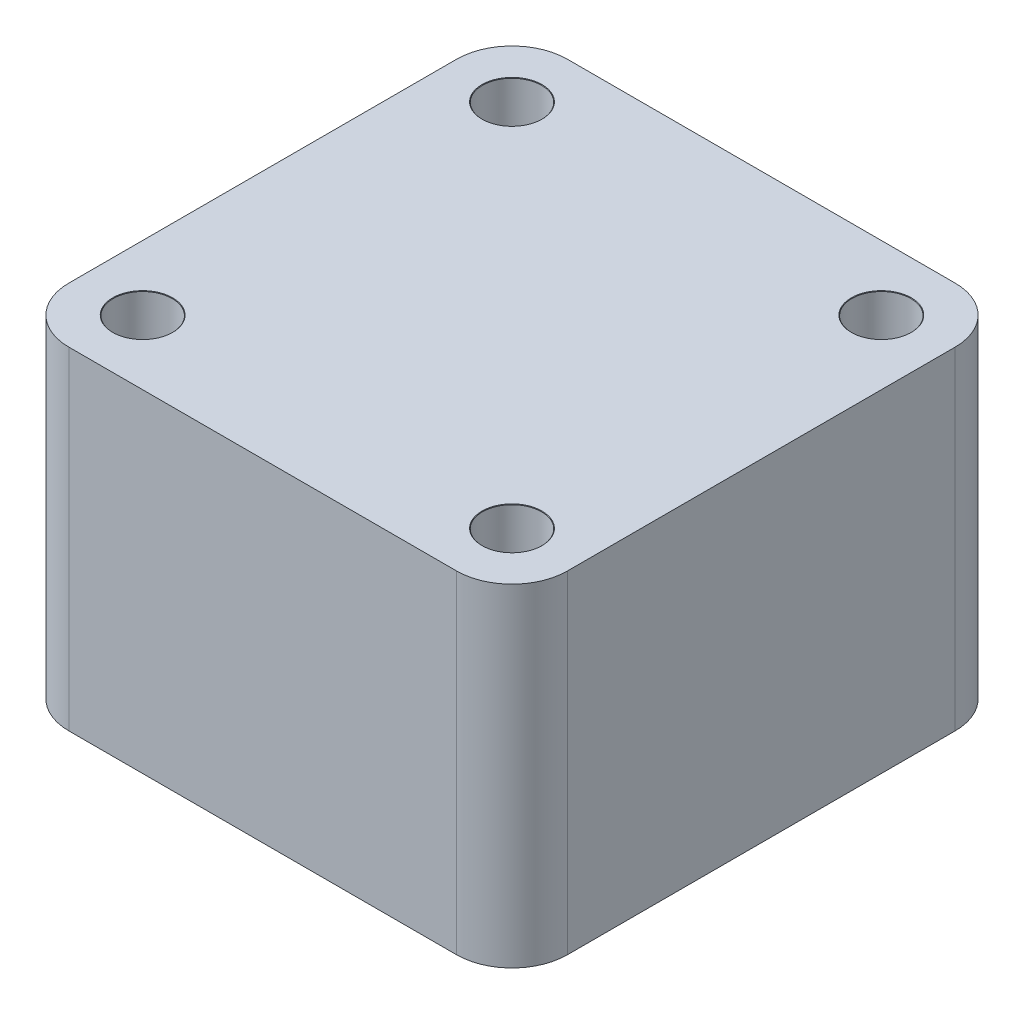
SolidWorks part; units mm, degrees
material "AISI 1045 Steel, cold drawn"
ref_plane "Front Plane" through (0, 0, 0) normal (0, 0, 1) x (1, 0, 0)
ref_plane "Top Plane" through (0, 0, 0) normal (0, 1, 0) x (1, 0, 0)
ref_plane "Right Plane" through (0, 0, 0) normal (1, 0, 0) x (0, 0, -1)
sketch "Sketch1" plane through (0, 0, 0) normal (0, 1, 0) x (1, 0, 0)
  line L1 (13.5, -13.5) -> (-13.5, -13.5)
  line L2 (13.5, -13.5) -> (13.5, 13.5)
  line L3 (13.5, 13.5) -> (-13.5, 13.5)
  line L4 (-13.5, -13.5) -> (-13.5, 13.5)
  line L5 (13.5, -13.5) -> (-13.5, 13.5) construction
  line L6 (13.5, 13.5) -> (-13.5, -13.5) construction
  line L7 (10, -10) -> (-10, -10) construction
  line L8 (10, -10) -> (10, 10) construction
  line L9 (10, 10) -> (-10, 10) construction
  line L10 (-10, -10) -> (-10, 10) construction
  line L11 (10, -10) -> (-10, 10) construction
  line L12 (10, 10) -> (-10, -10) construction
  point P0 (0, 0)
  point P6 (0, 0)
  dimension "D1" = 20
  dimension "D2" = 27
extrude "Boss-Extrude1" add sketch "Sketch1" along normal blind 18
hole_wizard "M3 Clearance Hole1" positions "Sketch2" profile "Sketch4" hole size "M3" standard "ANSI Metric" end condition through all
sketch "Sketch2" plane through (0, 0, 0) normal (0, -1, 0) x (-1, 0, 0)
  point P0 (-10, 10)
  point P3 (10, 10)
  point P6 (10, -10)
  point P9 (-10, -10)
sketch "Sketch4" plane through (10, 0, -10) normal (1, 0, 0) x (0, 0, -1)
  line L0 (0, 0) -> (0, 18)
  line L1 (0, 18) -> (1.625, 18)
  line L2 (1.6, 17.975) -> (1.6, 0.025)
  line L3 (1.6, 0.025) -> (1.625, 0)
  line L5 (1.625, 0) -> (0, 0)
  line L6 (-1.6, 0.025) -> (-1.625, 0) construction
  line L7 (1.625, 18) -> (1.6, 17.975)
  line L8 (-1.625, 18) -> (-1.6, 17.975) construction
  line L11 (0, -6.35) -> (0, 107.95) construction
  dimension "Thru Hole Dia." = 3.2
  dimension "Thru Hole Depth" = 18
  dimension "Near C'Sink Dia." = 3.25
  dimension "Near C'Sink Angle" = 90
  dimension "Far C'Sink Dia." = 3.25
  dimension "Far C'Sink Angle" = 90
fillet "Fillet1" radius 3 4 edges at (13.5, 9, 13.5) (-13.5, 9, 13.5) (13.5, 9, -13.5) (-13.5, 9, -13.5)
